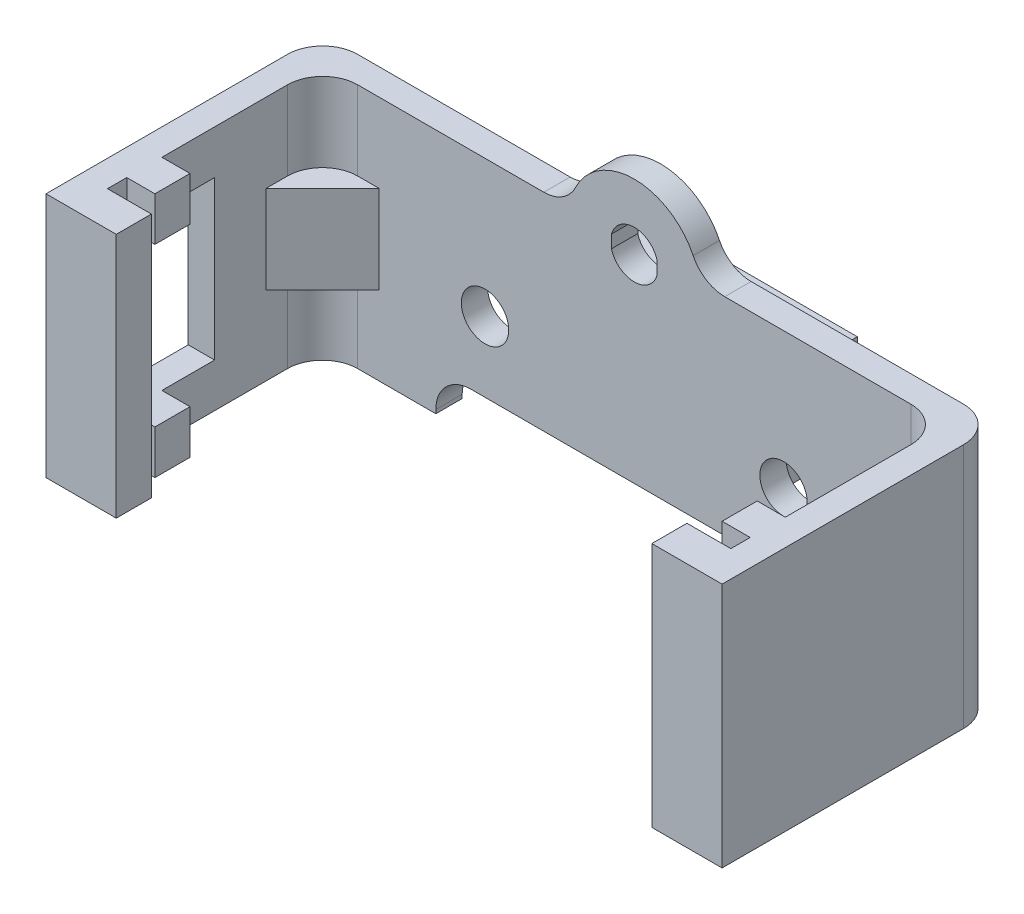
SolidWorks part; units mm, degrees
ref_plane "前视基准面" through (0, 0, 0) normal (0, 0, 1) x (1, 0, 0)
ref_plane "上视基准面" through (0, 0, 0) normal (0, 1, 0) x (1, 0, 0)
ref_plane "右视基准面" through (0, 0, 0) normal (1, 0, 0) x (0, 0, -1)
sketch "草图1" plane through (0, 0, 0) normal (0, 0, 1) x (1, 0, 0)
  line L1 (-13.5, -8.5) -> (13.5, -8.5)
  line L2 (-13.5, -8.5) -> (-13.5, 8.5)
  line L3 (-13.5, 8.5) -> (13.5, 8.5)
  line L4 (13.5, -8.5) -> (13.5, 8.5)
  line L5 (-13.5, -8.5) -> (13.5, 8.5) construction
  line L6 (-13.5, 8.5) -> (13.5, -8.5) construction
  point P0 (0, 0)
  dimension "D1" = 27
  dimension "D2" = 17
extrude "凸台-拉伸1" add sketch "草图1" along normal blind 1
sketch "草图2" plane through (0, 0, 1) normal (0, 0, 1) x (1, 0, 0)
  line L0 (-8.27, 4.125) -> (8.27, 4.125) construction
  line L3 (0, 1.575) -> (0, -1.575) construction
  line L4 (8.27, 4.125) -> (8.27, -4.125) construction
  line L5 (8.27, -4.125) -> (-8.27, -4.125) construction
  line L6 (-8.27, -4.125) -> (-8.27, 4.125) construction
  circle A0 centre (0, 4.125) radius 2.55
  circle A1 centre (0, -4.125) radius 2.55
  circle A2 centre (8.27, 4.125) radius 2.55
  circle A3 centre (8.27, -4.125) radius 2.55
  circle A4 centre (-8.27, 4.125) radius 2.55
  circle A5 centre (-8.27, -4.125) radius 2.55
  point P2 (0, 1.575)
  point P5 (0, -1.575)
  point P6 (0, 0)
  point P11 (-2.55, 4.125)
  point P20 (-5.72, 4.125)
  dimension "D1" = 5.1
  dimension "D4" = 3.17
  dimension "D2" = 3.15
extrude "切除-拉伸1" cut sketch "草图2" against normal through all
sketch "草图3" plane through (0, -8.5, 0) normal (0, -1, 0) x (1, 0, 0)
  line L0 (13.5, 0) -> (19, 0)
  line L1 (13.5, 1) -> (13.5, 0)
  line L2 (20.5, 1) -> (13.5, 1)
  line L3 (20.5, 1) -> (20.5, -30)
  line L4 (-13.5, 1) -> (-13.5, 0) construction
  line L5 (19, -28.5) -> (19, 0)
  line L6 (-13.5, -28.5) -> (-13.5, -30)
  line L7 (-13.5, -30) -> (20.5, -30)
  line L9 (-13.5, -28.5) -> (19, -28.5)
  dimension "D1" = 7
  dimension "D2" = 1.5
  dimension "D3" = 1.5
  dimension "D4" = 30
extrude "凸台-拉伸2" add sketch "草图3" against normal up to surface (17 mm away) up to face at (0, 8.5, 0.5)
sketch "草图6" plane through (0, 0, 0) normal (0, 1, 0) x (1, 0, 0)
  line L0 (19, 0) -> (19, 5)
  line L1 (19, 28.5) -> (19, 0) construction
  line L2 (19, 5) -> (14, 0)
  line L3 (19, 0) -> (-13.5, 0) construction
  line L4 (14, 0) -> (19, 0)
  line L5 (19, 28.5) -> (14, 28.5)
  line L6 (-13.5, 28.5) -> (19, 28.5) construction
  line L7 (14, 28.5) -> (19, 23.5)
  line L8 (19, 23.5) -> (19, 28.5)
  line L9 (20.5, 30) -> (-13.5, 30) construction
  line L10 (19, 19) -> (17.5, 19)
  line L11 (19, 19) -> (19, 21)
  line L12 (19, 21) -> (17.5, 21)
  line L13 (17.5, 19) -> (17.5, 21)
  point P18 (17.5, 20)
  dimension "D1" = 5
  dimension "D2" = 5
  dimension "D3" = 5
  dimension "D4" = 5
  dimension "D5" = 10
  dimension "D6" = 1.5
  dimension "D7" = 2
extrude "凸台-拉伸3" add sketch "草图6" along normal mid plane 4
chamfer "倒角1" distance 1 angle 45 1 edges at (-13.5, 0, 0)
sketch "草图8" plane through (0, 0, 0) normal (0, 0, -1) x (-1, 0, 0)
  circle A0 centre (0, 0) radius 2
  dimension "D1" = 4
extrude "切除-拉伸4" cut sketch "草图8" against normal up to next
fillet "圆角1" radius 3 6 edges at (20.5, 0, -30) (20.5, 0, 1) (19, 5.25, 0) (19, -5.25, 0) (19, 5.25, -28.5) (19, -5.25, -28.5)
sketch "草图9" plane through (0, 0, -30) normal (0, 0, -1) x (-1, 0, 0)
  line L1 (-3.5, 13) -> (3.5, 13)
  line L2 (-3.5, 13) -> (-3.5, 0)
  line L3 (-3.5, 0) -> (3.5, 0)
  line L4 (3.5, 13) -> (3.5, 0)
  point P4 (0, 0)
  dimension "D1" = 7
  dimension "D2" = 13
extrude "凸台-拉伸4" add sketch "草图9" against normal up to surface (1.5 mm away) up to face at (8.125, 0, -28.5)
sketch "草图7" plane through (0, 0, -30) normal (0, 0, -1) x (-1, 0, 0)
  line L0 (0, 0) -> (0, 10) construction
  line L1 (-8.5, 2.7) -> (8.5, 2.7) construction
  circle A0 centre (0, 0) radius 1.35 construction
  circle A1 centre (0, 10) radius 1.35
  circle A3 centre (-8.5, 2.7) radius 1.35
  circle A4 centre (8.5, 2.7) radius 1.35
  point P9 (0, 2.7)
  dimension "D1" = 2.7
  dimension "D5" = 2.7
  dimension "D6" = 2.7
  dimension "D2" = 10
  dimension "D3" = 2.7
  dimension "D4" = 17
extrude "切除-拉伸5" cut sketch "草图7" against normal blind 10
sketch "草图11" plane through (0, 0, -30) normal (0, 0, -1) x (-1, 0, 0)
  line L2 (13.5, 0) -> (-17.5, 0)
  line L3 (13.5, 8.5) -> (13.5, -8.5) construction
  line L4 (-17.5, 8.5) -> (-17.5, -8.5) construction
  line L5 (-17.5, 0) -> (-17.5, -8.5)
  line L6 (-17.5, -8.5) -> (13.5, -8.5)
  line L7 (13.5, -8.5) -> (13.5, 0)
  arc A1 (-17.5, -8.5) -> (-9, 0) centre (-9, -8.5) cw
  line M4 (13.5, -8.5) -> (13.5, 8.5)
  line M16 (-17.5, -8.5) -> (13.5, -8.5)
extrude "切除-拉伸6" cut sketch "草图11" against normal up to next contours A1 L2 M16 M4 region at (1.1496, -4.397, -30)
fillet "圆角2" radius 2.2 6 edges at (-13.5, 8.5, -29.25) (-3.5, 8.5, -29.25) (3.5, 8.5, -29.25) (-3.5, 13, -29.25) (3.5, 13, -29.25) (-13.5, 0, -29.25)
sketch "草图13" plane through (0, 0, -30) normal (0, 0, -1) x (-1, 0, 0)
  line L0 (11.3, 0) -> (-9, 0) construction
  line L1 (-11.2, 5.4) -> (-5.8, 5.4)
  line L2 (-11.2, 5.4) -> (-11.2, 0)
  line L3 (-11.2, 0) -> (-5.8, 0)
  line L4 (-5.8, 5.4) -> (-5.8, 0)
  line L5 (-11.2, 5.4) -> (-5.8, 0) construction
  line L6 (-11.2, 0) -> (-5.8, 5.4) construction
  line L11 (11.2, 0) -> (5.8, 0)
  line L12 (11.2, 0) -> (11.2, 5.4)
  line L18 (-5.8, 5.4) -> (5.8, 5.4)
  line L19 (11.2, 5.4) -> (5.8, 5.4)
  line L20 (5.8, 0) -> (5.8, 5.4)
  line L21 (11.2, 0) -> (5.8, 5.4) construction
  line L22 (11.2, 5.4) -> (5.8, 0) construction
  line L23 (-5.8, 5.4) -> (-5.8, 0)
  line L24 (-5.8, 0) -> (5.8, 0)
  line L25 (5.8, 5.4) -> (5.8, 0)
  point P0 (-8.5, 2.7)
  point P6 (8.5, 2.7)
  point P12 (0.1939, 2.7)
  line M20 (-9, 0) -> (11.3, 0)
extrude "凸台-拉伸6" add sketch "草图13" along normal blind 5.4 contours L20 L18 L4 M20 region at (0, 2.7, -30)
sketch "草图14" plane through (0, 8.5, 0) normal (0, 1, 0) x (1, 0, 0)
  line L0 (-1.3, 28.5) -> (1.3, 28.5) construction
  line L1 (-13.5, 35.4) -> (13.5, 35.4)
  line L2 (-13.5, 35.4) -> (-13.5, 28.5)
  line L3 (-13.5, 28.5) -> (13.5, 28.5)
  line L4 (13.5, 35.4) -> (13.5, 28.5)
  line L5 (-3.5, 28.5) -> (-1.3, 28.5) construction
  line L6 (5.8, 35.4) -> (-5.8, 35.4) construction
  line L7 (-13.5, 28.5) -> (-13.5, 30) construction
  point P5 (0, 28.5)
  point P8 (0, 28.5)
extrude "切除-拉伸7" cut sketch "草图14" against normal through all both and the other way through all flip side to cut
sketch "草图15" plane through (0, 0, 0) normal (0, -1, 0) x (1, 0, 0)
  line L0 (-11.3, -30) -> (-5.8, -30) construction
  line L1 (-19.25, -30) -> (19.25, -30)
  line L2 (-19.25, -30) -> (-19.25, -14.25)
  line L3 (-19.25, -14.25) -> (19.25, -14.25)
  line L4 (19.25, -30) -> (19.25, -14.25)
  line L5 (-17.75, -14.25) -> (17.75, -14.25)
  line L6 (-17.75, -14.25) -> (-17.75, -28.5)
  line L7 (-17.75, -28.5) -> (17.75, -28.5)
  line L8 (17.75, -14.25) -> (17.75, -28.5)
  line L9 (-11.3, -28.5) -> (9, -28.5) construction
  line L10 (0, -14.25) -> (0, -35.4) construction
  line L11 (5.8, -35.4) -> (-5.8, -35.4) construction
  line L12 (13.5, -28.5) -> (13.5, -30)
  line L13 (-17.75, -17.35) -> (-16.15, -17.35)
  line L14 (-17.75, -17.35) -> (-17.75, -19.35)
  line L15 (-17.75, -19.35) -> (-16.15, -19.35)
  line L16 (-16.15, -17.35) -> (-16.15, -19.35)
  line L17 (-17.75, -14.25) -> (-15.25, -14.25)
  line L18 (-17.75, -14.25) -> (-17.75, -16.25)
  line L19 (-17.75, -16.25) -> (-15.25, -16.25)
  line L20 (-15.25, -14.25) -> (-15.25, -16.25)
  line L21 (15.25, -14.25) -> (17.75, -14.25)
  line L22 (15.25, -14.25) -> (15.25, -16.25)
  line L23 (15.25, -16.25) -> (17.75, -16.25)
  line L24 (17.75, -14.25) -> (17.75, -16.25)
  line L25 (16.15, -17.35) -> (17.75, -17.35)
  line L26 (16.15, -17.35) -> (16.15, -19.35)
  line L27 (16.15, -19.35) -> (17.75, -19.35)
  line L28 (17.75, -17.35) -> (17.75, -19.35)
  line L29 (13.5, -30) -> (13.5, -28.5) construction
  point P17 (0, -14.25)
  line M27 (-11.3, -28.5) -> (-11.3, -30)
  line M33 (9, -30) -> (9, -28.5)
  dimension "D2" = 1.5
  dimension "D3" = 1.1
  dimension "D4" = 1.6
  dimension "D5" = 1.6
  dimension "D6" = 2
  dimension "D7" = 2.5
  dimension "D8" = 2
  dimension "D9" = 12.25
  dimension "D10" = 2.5
  dimension "D11" = 38.5
extrude "凸台-拉伸7" add sketch "草图15" against normal blind 10.5 and the other way blind 3.5 contours L3 L8 L7 L1 L4 M33 | L20 L3 L6 L19 | L16 L13 L6 L15 | L7 L6 L3 L2 L1 M27 | L22 L23 L8 L3 | L26 L27 L28 L25 region at (-19.0736, 0, -22.125) region at (-16.5, 0, -15.25) region at (17.8891, 0, -23.6391) region at (-16.95, 0, -18.35) region at (16.5, 0, -15.25)
sketch "草图16" plane through (0, 8.5, 0) normal (0, 1, 0) x (1, 0, 0)
  line L0 (-1.3, 30) -> (-1.3, 28.5)
  line L1 (-11.3, 30) -> (13.5, 30)
  line L2 (-11.3, 30) -> (-11.3, 28.5)
  line L3 (-11.3, 28.5) -> (13.5, 28.5)
  line L4 (13.5, 30) -> (13.5, 28.5)
  line L6 (1.3, 30) -> (1.3, 28.5)
  line M5 (-5.7, 30) -> (-11.3, 30)
  line M6 (-11.3, 30) -> (-11.3, 28.5)
  line M7 (-11.3, 28.5) -> (-5.7, 28.5)
  line M8 (-5.7, 28.5) -> (-5.7, 30)
extrude "凸台-拉伸8" add sketch "草图16" along normal up to surface (2 mm away) contours M8 M5 M6 M7 | L3 L0 L1 M8 | L1 L6 L3 L4 region at (-3.5, 8.5, -29.25) region at (-8.5, 8.5, -29.25) region at (7.4, 8.5, -29.25) up to face at (-16.2417, 10.5, -20.95)
ref_plane "基准面1" through (0, 3.5, 0) normal (0, -1, 0) x (-1, 0, 0)
sketch "草图17" plane through (0, 3.5, 0) normal (0, -1, 0) x (-1, 0, 0)
  line L0 (17.75, 25.275) -> (14.525, 28.5)
  line L1 (17.75, 19.35) -> (17.75, 28.5) construction
  line L2 (17.75, 28.5) -> (11.3, 28.5) construction
  line L3 (14.525, 28.5) -> (17.75, 28.5)
  line L4 (17.75, 28.5) -> (17.75, 25.275)
  line L5 (-17.75, 25.275) -> (-17.75, 28.5)
  line L6 (-17.75, 19.35) -> (-17.75, 28.5) construction
  line L7 (-17.75, 28.5) -> (-14.525, 28.5)
  line L8 (-13.5, 28.5) -> (-17.75, 28.5) construction
  line L9 (-14.525, 28.5) -> (-17.75, 25.275)
extrude "凸台-拉伸9" add sketch "草图17" along normal mid plane 5
sketch "草图18" plane through (-19.25, 0, 0) normal (-1, 0, 0) x (0, 0, 1)
  line L0 (-17.35, -3.5) -> (-17.35, 10.5) construction
  line L1 (-17.35, 8) -> (-22.35, 8)
  line L2 (-17.35, 8) -> (-17.35, -1)
  line L3 (-17.35, -1) -> (-22.35, -1)
  line L4 (-22.35, 8) -> (-22.35, -1)
  line L5 (-14.25, -3.5) -> (-14.25, 10.5) construction
  point P8 (-22.35, 3.5)
  point P9 (-14.25, 3.5)
  dimension "D1" = 9
  dimension "D2" = 5
extrude "切除-拉伸8" cut sketch "草图18" against normal up to next
sketch "草图19" plane through (0, 0, -28.5) normal (0, 0, 1) x (1, 0, 0)
  line L1 (-11.3, 0) -> (13.5, 0)
  line L2 (-11.3, 0) -> (-11.3, -1.2889)
  line L3 (-11.3, -1.2889) -> (13.5, -1.2889)
  line L4 (13.5, 0) -> (13.5, -1.2889)
  circle A0 centre (0, 10) radius 3.7264
  arc A1 (3.5, 10.8) -> (1.3, 13) centre (1.3, 10.8) ccw construction
  circle A2 centre (0, 10) radius 1.35
  arc A3 (-1.3, 9.636) -> (1.3, 9.636) centre (0, 10) ccw construction
extrude "凸台-拉伸10" add sketch "草图19" against normal up to surface (1.5 mm away) up to face at (0, 10, -30)
fillet "圆角4" radius 2 12 edges at (0, 5.4, -30) (3.6927, 10.5, -29.25) (-3.6927, 10.5, -29.25) (19.25, 3.5, -30) (-19.25, 3.5, -30) (-11.3, -1.2889, -29.25) (13.5, -1.2889, -29.25) (17.75, -1.25, -28.5) (17.75, 8.25, -28.5) (-17.75, 8.25, -28.5) (-17.75, -1.25, -28.5) (0, 0, -30)
